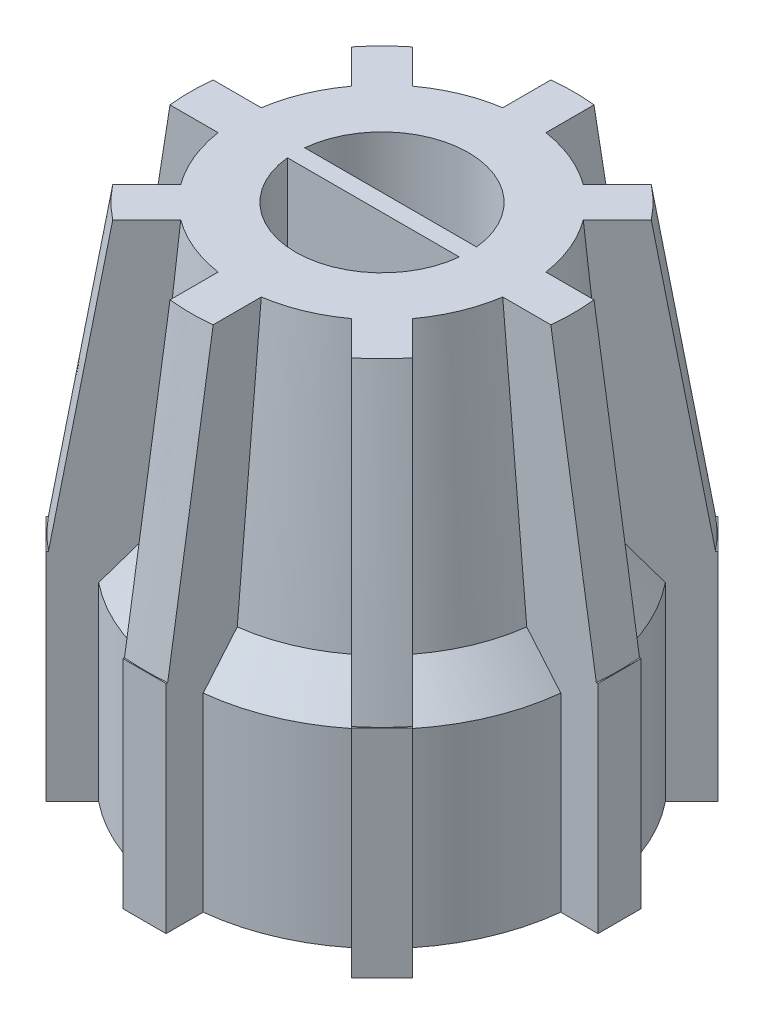
SolidWorks part; units mm, degrees
ref_plane "Front Plane" through (0, 0, 0) normal (0, 0, 1) x (1, 0, 0)
ref_plane "Top Plane" through (0, 0, 0) normal (0, 1, 0) x (1, 0, 0)
ref_plane "Right Plane" through (0, 0, 0) normal (1, 0, 0) x (0, 0, -1)
sketch "Sketch1" plane through (0, 0, 0) normal (0, 1, 0) x (1, 0, 0)
  line L0 (-2.985, -0.3) -> (2.985, -0.3)
  line L1 (-2.985, 0.3) -> (2.985, 0.3)
  line L2 (0, 0) -> (-2.985, 0) construction
  arc A0 (-2.985, -0.3) -> (2.985, -0.3) centre (0, 0) ccw
  arc A1 (2.985, 0.3) -> (-2.985, 0.3) centre (0, 0) ccw
  circle A2 centre (0, 0) radius 8.5
  dimension "D2" = 6
  dimension "D3" = 17
  dimension "D1" = 0.6
extrude "Boss-Extrude1" add sketch "Sketch1" along normal blind 11.5
sketch "Sketch3" plane through (0, 0, 0) normal (1, 0, 0) x (0, 0, -1)
  line L0 (8.5, 11.5) -> (-8.5, 11.5) construction
  line L3 (0, 0) -> (0, 12.7) construction
  line L4 (-8.5, 0) -> (8.5, 0) construction
  line L5 (-8.5, 0) -> (-8.5, 11.5)
  line L6 (-8.5, 11.5) -> (-5, 11.5)
  line L7 (5, 11.5) -> (8.5, 11.5)
  line L8 (8.5, 11.5) -> (8.5, 0)
  line L10 (-5, 11.5) -> (-6, 0)
  line L13 (-6, 0) -> (-8.5, 0)
  line L14 (5, 11.5) -> (6, 0)
  line L15 (6, 0) -> (8.5, 0)
  line L16 (-8.5, 11.5) -> (-8.5, 0) construction
  dimension "D1" = 10
  dimension "D2" = 12
revolve "Cut-Revolve1" cut sketch "Sketch3" angle 360 about L3
sketch "Sketch4" plane through (0, 0, 0) normal (0, -1, 0) x (1, 0, 0)
  circle A0 centre (0, 0) radius 7
  circle A1 centre (0, 0) radius 5.5
  dimension "D1" = 14
  dimension "D2" = 11
extrude "Boss-Extrude3" add sketch "Sketch4" along normal blind 6
chamfer "Chamfer1" distance 2 angle 35 1 edges at (0, 0, -6)
chamfer "Chamfer2" distance 2 angle 45 1 edges at (0, 0, -5.5)
sketch "Sketch5" plane through (0, 11.5, 0) normal (0, 1, 0) x (1, 0, 0)
  line L1 (-8.25, -0.75) -> (8.25, -0.75)
  line L2 (-8.25, -0.75) -> (-8.25, 0.75)
  line L3 (-8.25, 0.75) -> (8.25, 0.75)
  line L4 (8.25, -0.75) -> (8.25, 0.75)
  line L5 (-8.25, -0.75) -> (8.25, 0.75) construction
  line L6 (-8.25, 0.75) -> (8.25, -0.75) construction
  circle A0 centre (0, 0) radius 5
  point P0 (0, 0)
  circle M7 centre (0, 0) radius 5
  dimension "D1" = 1.5
  dimension "D2" = 16.5
extrude "Boss-Extrude5" add sketch "Sketch5" against normal up to surface (17.5 mm away) contours L3 L2 L1 M7 | L1 L4 L3 M7 up to face at (0, -6, -7)
pattern_circular "CirPattern1" count 8 over 360 about axis through (0, 0, 0) along (0, 1, 0) of "Boss-Extrude5"
sketch "Sketch6" plane through (0, -6, 0) normal (0, -1, 0) x (1, 0, 0)
  circle A0 centre (0, 0) radius 5.5
extrude "Cut-Extrude1" cut sketch "Sketch6" against normal up to vertex (4 mm away) contours A0
sketch "Sketch7" plane through (0, 0, 0) normal (1, 0, 0) x (0, 0, -1)
  line L0 (0, -6) -> (0, 11.5) construction
  line L1 (-0.75, -6) -> (0.75, -6) construction
  line L2 (-0.75, 11.5) -> (0.75, 11.5) construction
  line L3 (-6.6571, 11.5) -> (-8.229, 1.5248)
  line L5 (-8.229, 11.5) -> (-6.6571, 11.5)
  line L8 (-8.229, 11.5) -> (-14.4101, 11.5)
  line L10 (-8.229, 1.5248) -> (-14.4101, 1.5248)
  line L11 (-14.4101, 11.5) -> (-14.4101, 1.5248)
revolve "Cut-Revolve5" cut sketch "Sketch7" angle 360 about L0
